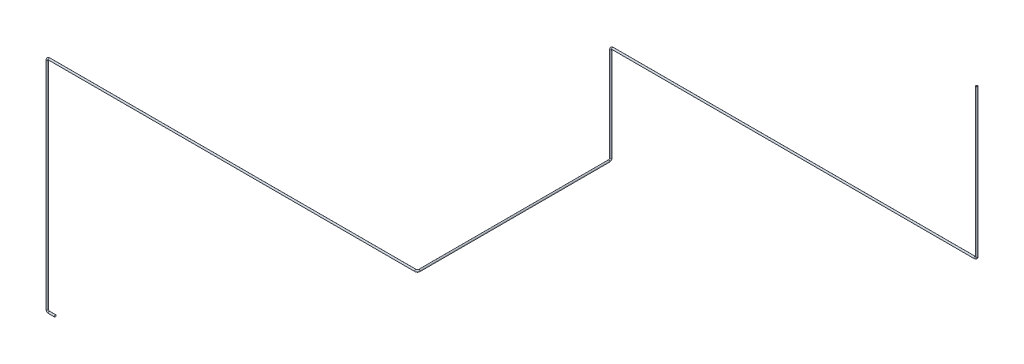
SolidWorks part; units mm, degrees
ref_plane "Plano frontal" through (0, 0, 0) normal (0, 0, 1) x (1, 0, 0)
ref_plane "Plano superior" through (0, 0, 0) normal (0, 1, 0) x (1, 0, 0)
ref_plane "Plano direito" through (0, 0, 0) normal (1, 0, 0) x (0, 0, -1)
sketch3d "3DSketch1"
  line L0 (-22023.7893, -6172.5994, 38950.2493) -> (-21783.3113, -6172.5994, 38950.2493) construction
  line L1 (-22023.7893, -7872.6822, 38950.2493) -> (-22023.7893, -6172.5994, 38950.2493) construction
  line L2 (-21783.3113, -6172.5994, 38950.2493) -> (-21783.3113, -8593.9208, 38950.2493)
  line L3 (-21813.3113, -8623.9208, 38950.2493) -> (-27753.5298, -8623.9208, 38950.2493)
  line L4 (-27783.5298, -8653.9208, 38950.2493) -> (-27783.5298, -10192.4379, 38950.2493)
  line L5 (-27783.5298, -10222.4379, 38980.2493) -> (-27783.5298, -10222.4379, 42091.7002)
  line L6 (-27813.5298, -10222.4379, 42121.7002) -> (-33823.2649, -10222.4379, 42121.7002)
  line L7 (-33853.2649, -10252.4379, 42121.7002) -> (-33853.2649, -13792.0136, 42121.7002)
  line L8 (-33823.2649, -13822.0136, 42121.7002) -> (-33723.2649, -13822.0136, 42121.7002)
  arc A0 (-33823.2649, -13822.0136, 42121.7002) -> (-33853.2649, -13792.0136, 42121.7002) centre (-33823.2649, -13792.0136, 42121.7002) ccw
  arc A1 (-33853.2649, -10252.4379, 42121.7002) -> (-33823.2649, -10222.4379, 42121.7002) centre (-33823.2649, -10252.4379, 42121.7002) ccw
  arc A2 (-27813.5298, -10222.4379, 42121.7002) -> (-27783.5298, -10222.4379, 42091.7002) centre (-27813.5298, -10222.4379, 42091.7002) ccw
  arc A3 (-27783.5298, -10222.4379, 38980.2493) -> (-27783.5298, -10192.4379, 38950.2493) centre (-27783.5298, -10192.4379, 38980.2493) ccw
  arc A4 (-27783.5298, -8653.9208, 38950.2493) -> (-27753.5298, -8623.9208, 38950.2493) centre (-27753.5298, -8653.9208, 38950.2493) ccw
  arc A5 (-21813.3113, -8623.9208, 38950.2493) -> (-21783.3113, -8593.9208, 38950.2493) centre (-21813.3113, -8593.9208, 38950.2493) ccw
  point P11 (-33964.8233, -10218.1652, 42105.4184)
  point P12 (-27783.5298, -10218.1652, 42081.6302)
  point P13 (-33844.5966, -13785.8269, 41905.5319)
  point P14 (-33656.0523, -13838.9271, 41928.4609)
  point P17 (-33853.2649, -13822.0136, 42121.7002)
  point P18 (-33823.2649, -13792.0136, 42091.7002)
  point P21 (-33853.2649, -10222.4379, 42121.7002)
  point P22 (-33823.2649, -10252.4379, 42091.7002)
  point P25 (-27783.5298, -10222.4379, 42121.7002)
  point P26 (-27813.5298, -10192.4379, 42091.7002)
  point P29 (-27783.5298, -10222.4379, 38950.2493)
  point P30 (-27753.5298, -10192.4379, 38980.2493)
  point P33 (-27783.5298, -8623.9208, 38950.2493)
  point P34 (-27753.5298, -8653.9208, 38920.2493)
  point P37 (-21783.3113, -8623.9208, 38950.2493)
  point P38 (-21813.3113, -8593.9208, 38980.2493)
  point P39 (0, 0, 0)
  point P40 (0, 0, 0)
  point P41 (-33613.4177, -13822.0136, 42121.7002)
  point P43 (0, 0, 0)
  point P44 (0, 0, 0)
  point P45 (0, 0, 0)
  point P47 (0, 0, 0)
  point P48 (0, 0, 0)
  point P49 (0, 0, 0)
  dimension "D1" = 30
sweep "Sweep-Thin1" add path "3DSketch1" circular profile diameter 30 parameters "D1"=1, "D3"=30
